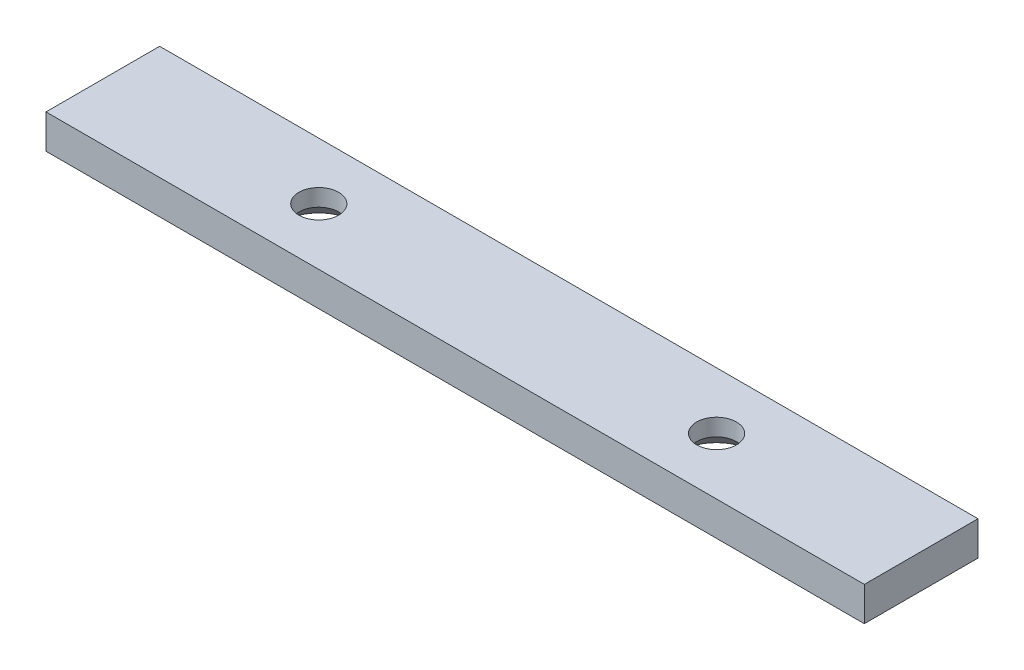
SolidWorks part; units mm, degrees
ref_plane "Front Plane" through (0, 0, 0) normal (0, 0, 1) x (1, 0, 0)
ref_plane "Top Plane" through (0, 0, 0) normal (0, 1, 0) x (1, 0, 0)
ref_plane "Right Plane" through (0, 0, 0) normal (1, 0, 0) x (0, 0, -1)
sketch "Sketch2" plane through (0, 0, 0) normal (0, 1, 0) x (1, 0, 0)
  line L1 (-72, -10) -> (72, -10)
  line L2 (-72, -10) -> (-72, 10)
  line L3 (-72, 10) -> (72, 10)
  line L4 (72, -10) -> (72, 10)
  line L5 (-72, -10) -> (72, 10) construction
  line L6 (-72, 10) -> (72, -10) construction
  circle A0 centre (-34, 0) radius 3.5
  circle A1 centre (36, 0) radius 3.5
  point P0 (0, 0)
  dimension "D3" = 7
  dimension "D6" = 7
  dimension "D1" = 144
  dimension "D2" = 20
  dimension "D4" = 38
  dimension "D5" = 70
extrude "Boss-Extrude1" add sketch "Sketch2" along normal mid plane 6 contours A0 | A1 | L1 L4 L3 L2 A1 A0 region at (-0.0275, 0, 0) region at (-34, 0, 0) region at (36, 0, 0)
extrude "Cut-Extrude1" cut sketch "Sketch2<3>" against normal through all draft 45 contours A0 | A1 region at (-34, 0, 0) region at (36, 0, 0) draft outward yes
sketch "Sketch2<3>" plane through (0, 0, 0) normal (0, 1, 0) x (1, 0, 0) same geometry as "Sketch2"
sketch "Sketch3" plane through (0, 0, 0) normal (0, -1, 0) x (1, 0, 0)
  circle A0 centre (36, 0) radius 3.5 construction
  circle A1 centre (-34, 0) radius 3.5 construction
  circle A2 centre (36, 0) radius 3.5
  circle A3 centre (-34, 0) radius 3.5
extrude "Cut-Extrude2" cut sketch "Sketch3" against normal through all
